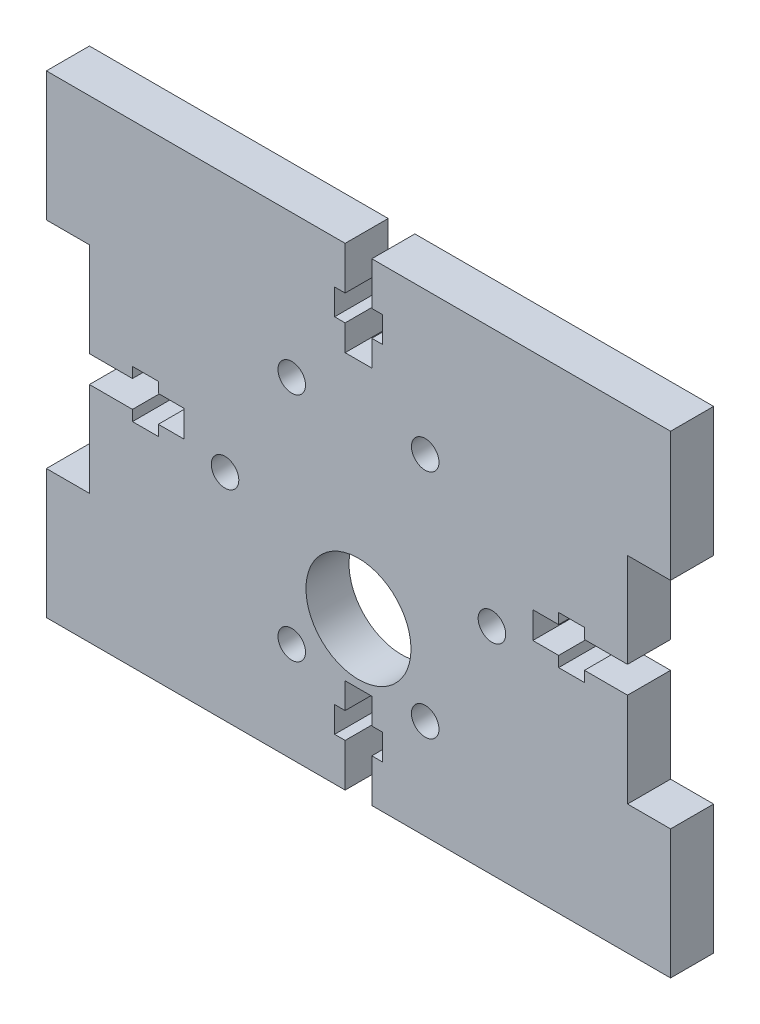
SolidWorks part; units mm, degrees
ref_plane "Plan de face" through (0, 0, 0) normal (0, 0, 1) x (1, 0, 0)
ref_plane "Plan de dessus" through (0, 0, 0) normal (0, 1, 0) x (1, 0, 0)
ref_plane "Plan de droite" through (0, 0, 0) normal (1, 0, 0) x (0, 0, -1)
ref_plane "Plan1" through (0, 0, 0) normal (0, 0, -1) x (-1, 0, 0)
sketch "Esquisse1" plane through (0, 0, 0) normal (0, 0, -1) x (-1, 0, 0)
  line L0 (-4.9964, 30) -> (-31.25, 30)
  line L1 (-31.25, 30) -> (-31.25, -25)
  line L2 (-31.25, -25) -> (-4.9964, -25)
  line L3 (-4.9964, -25) -> (-4.9964, 30)
extrude "Boss.-Extru.1" add sketch "Esquisse1" against normal blind 5
sketch "Esquisse2" plane through (31.25, 0, 0) normal (1, 0, 0) x (0, 0, -1)
  line L0 (0, 15) -> (-2.05, 15)
  line L1 (-2.05, 15) -> (-5, 17.95)
  line L2 (-5, 17.95) -> (-5, 30)
  line L3 (-5, 30) -> (0, 30)
  line L4 (0, 30) -> (0, 15)
extrude "Boss.-Extru.2" add sketch "Esquisse2" along normal blind 5
sketch "Esquisse3" plane through (31.25, 0, 0) normal (1, 0, 0) x (0, 0, -1)
  line L0 (-5, -12.95) -> (-2.05, -10)
  line L1 (-2.05, -10) -> (0, -10)
  line L2 (0, -10) -> (0, -25)
  line L3 (0, -25) -> (-5, -25)
  line L4 (-5, -25) -> (-5, -12.95)
extrude "Boss.-Extru.3" add sketch "Esquisse3" along normal blind 5
sketch "Esquisse4" plane through (0, 30, 0) normal (0, 1, 0) x (-1, 0, 0)
  line L0 (-4.9964, 5) -> (-7.9464, 5)
  line L1 (-7.9464, 5) -> (-4.9964, 2.05)
  line L2 (-4.9964, 2.05) -> (-4.9964, 5)
extrude "Enlèv. mat.-Extru.1" cut sketch "Esquisse4" against normal blind 5
sketch "Esquisse5" plane through (4.9964, 0, 0) normal (-1, 0, 0) x (0, 0, 1)
  line L0 (0, -25) -> (0, 25)
  line L1 (0, 25) -> (5, 25)
  line L2 (5, 25) -> (5, -25)
  line L3 (5, -25) -> (0, -25)
extrude "Boss.-Extru.4" add sketch "Esquisse5" along normal blind 36.2464
sketch "Esquisse6" plane through (-31.25, 0, 0) normal (-1, 0, 0) x (0, 0, 1)
  line L0 (0, -25) -> (0, -10)
  line L1 (0, -10) -> (2.05, -10)
  line L2 (2.05, -10) -> (5, -12.95)
  line L3 (5, -12.95) -> (5, -25)
  line L4 (5, -25) -> (0, -25)
extrude "Boss.-Extru.5" add sketch "Esquisse6" along normal blind 5
sketch "Esquisse7" plane through (-31.25, 0, 0) normal (-1, 0, 0) x (0, 0, 1)
  line L0 (0, 25) -> (5, 25)
  line L1 (5, 25) -> (5, 17.95)
  line L2 (5, 17.95) -> (2.05, 15)
  line L3 (2.05, 15) -> (0, 15)
  line L4 (0, 15) -> (0, 25)
extrude "Boss.-Extru.6" add sketch "Esquisse7" along normal blind 5
sketch "Esquisse8" plane through (0, 25, 0) normal (0, 1, 0) x (-1, 0, 0)
  line L0 (5.0006, 2.0542) -> (7.9464, 5)
  line L1 (7.9464, 5) -> (36.25, 5)
  line L2 (36.25, 5) -> (36.25, 0)
  line L3 (36.25, 0) -> (5.0006, 0)
  line L4 (5.0006, 0) -> (5.0006, 2.0542)
extrude "Boss.-Extru.7" add sketch "Esquisse8" along normal blind 5
hole_wizard "Diamètre du perçage Ø12.2 (12.2)1" positions "Esquisse10" profile "Esquisse9" hole size "Ø12.2" standard "Ansi Metric"
sketch "Esquisse10" plane through (0, 0, 5) normal (0, 0, 1) x (1, 0, 0)
  point P0 (0, -7)
sketch "Esquisse9" plane through (0, -7, 5) normal (1, 0, 0) x (0, -1, 0)
  line L0 (0, 0) -> (0, 5)
  line L1 (0, 5) -> (6.1, 5)
  line L2 (6.1, 5) -> (6.1, 0)
  line L5 (6.1, 0) -> (0, 0)
  line L11 (0, -6.35) -> (0, 107.95) construction
  dimension "Diamètre du perçage jusqu'au prochain" = 12.2
  dimension "Profondeur du perçage jusqu'au prochain" = 5
hole_wizard "Diamètre du perçage Ø3.2 (3.2)1" positions "Esquisse12" profile "Esquisse11" hole size "Ø3.2" standard "Ansi Metric" end condition through all
sketch "Esquisse12" plane through (0, 0, 5) normal (0, 0, 1) x (1, 0, 0)
  point P0 (-7.75, -13.4234)
  point P1 (15.5, 0)
  point P2 (-7.75, 13.4234)
  point P3 (7.75, 13.4234)
  point P4 (7.75, -13.4234)
  point P5 (-15.5, 0)
sketch "Esquisse11" plane through (-7.75, -13.4234, 5) normal (1, 0, 0) x (0, -1, 0)
  line L0 (0, 0) -> (0, 5)
  line L1 (0, 5) -> (1.6, 5)
  line L2 (1.6, 5) -> (1.6, 0)
  line L5 (1.6, 0) -> (0, 0)
  line L11 (0, -6.35) -> (0, 107.95) construction
  dimension "Diamètre du perçage jusqu'au prochain" = 3.2
  dimension "Profondeur du perçage jusqu'au prochain" = 5
fillet "Congé1" radius 1.6 6 edges at (4.9964, 27.5, 2.05) (33.75, -10, 2.05) (33.75, 15, 2.05) (-33.75, -10, 2.05) (-5.0006, 27.5, 2.0542) (-33.75, 15, 2.05) tangent propagation no
sketch "Esquisse13" plane through (0, 0, 5) normal (0, 0, 1) x (1, 0, 0)
  line L1 (-36.25, 17.95) -> (-31.25, 17.95)
  line L2 (-36.25, 17.95) -> (-36.25, 15)
  line L3 (-36.25, 15) -> (-31.25, 15)
  line L4 (-31.25, 17.95) -> (-31.25, 15)
  line L5 (-36.25, -10) -> (-31.25, -10)
  line L6 (-36.25, -10) -> (-36.25, -12.95)
  line L7 (-36.25, -12.95) -> (-31.25, -12.95)
  line L8 (-31.25, -10) -> (-31.25, -12.95)
  line L9 (-7.9464, 30) -> (-5.0006, 30)
  line L10 (-7.9464, 30) -> (-7.9464, 25)
  line L11 (-7.9464, 25) -> (-5.0006, 25)
  line L12 (-5.0006, 30) -> (-5.0006, 25)
  line L13 (4.9964, 30) -> (7.9464, 30)
  line L14 (4.9964, 30) -> (4.9964, 25)
  line L15 (4.9964, 25) -> (7.9464, 25)
  line L16 (7.9464, 30) -> (7.9464, 25)
  line L17 (31.25, 17.95) -> (36.25, 17.95)
  line L18 (31.25, 17.95) -> (31.25, 15)
  line L19 (31.25, 15) -> (36.25, 15)
  line L20 (36.25, 17.95) -> (36.25, 15)
  line L21 (31.25, -10) -> (36.25, -10)
  line L22 (31.25, -10) -> (31.25, -12.95)
  line L23 (31.25, -12.95) -> (36.25, -12.95)
  line L24 (36.25, -10) -> (36.25, -12.95)
  line L25 (-5.0006, 30) -> (4.9964, 30)
  line L26 (-5.0006, 30) -> (-5.0006, 25)
  line L27 (-5.0006, 25) -> (4.9964, 25)
  line L28 (4.9964, 30) -> (4.9964, 25)
  line M9 (7.9464, 30) -> (7.9464, 25)
  line M10 (7.9464, 25) -> (-7.9464, 25)
  line M11 (-7.9464, 25) -> (-7.9464, 30)
  line M14 (-36.25, 17.95) -> (-31.25, 17.95)
  line M15 (-31.25, 17.95) -> (-31.25, -12.95)
  line M16 (-31.25, -12.95) -> (-36.25, -12.95)
  line M20 (36.25, -12.95) -> (31.25, -12.95)
  line M21 (31.25, -12.95) -> (31.25, 17.95)
  line M22 (31.25, 17.95) -> (36.25, 17.95)
extrude "Boss.-Extru.8" add sketch "Esquisse13" against normal blind 5 contours L25 L12 L14 M10 | L12 L9 M11 M10 | L13 L14 M10 M9 | L20 L19 M22 M21 | L24 L21 M21 M20 | L5 L6 M16 M15 | L2 L3 M15 M14 region at (-33.75, -11.475, 5) region at (-33.75, 16.475, 5) region at (-6.4735, 27.5, 5) region at (-0.0021, 27.5, 5) region at (6.4714, 27.5, 5) region at (33.75, -11.475, 5) region at (33.75, 16.475, 5)
sketch "Esquisse14" plane through (0, 0, 5) normal (0, 0, 1) x (1, 0, 0)
  line L0 (1.55, 19) -> (-1.55, 19)
  line L1 (1.55, 19) -> (1.55, 30)
  line L2 (1.55, 30) -> (-1.55, 30)
  line L3 (-1.55, 19) -> (-1.55, 30)
  line L4 (2.78, 22) -> (-2.77, 22)
  line L5 (2.78, 22) -> (2.78, 25)
  line L6 (2.78, 25) -> (-2.77, 25)
  line L7 (-2.77, 22) -> (-2.77, 25)
  line L8 (-20.25, 0.95) -> (-31.25, 0.95)
  line L9 (-20.25, 0.95) -> (-20.25, 4.05)
  line L10 (-20.25, 4.05) -> (-31.25, 4.05)
  line L11 (-31.25, 0.95) -> (-31.25, 4.05)
  line L12 (-23.25, -0.28) -> (-26.25, -0.28)
  line L13 (-23.25, -0.28) -> (-23.25, 5.27)
  line L14 (-23.25, 5.27) -> (-26.25, 5.27)
  line L15 (-26.25, -0.28) -> (-26.25, 5.27)
  line L18 (-36.25, 30) -> (36.25, 30) construction
  line L19 (-31.25, -10) -> (-31.25, 15) construction
  line L20 (-31.25, -10) -> (-36.25, -10) construction
  line L21 (0, 0) -> (0, 11.8782) construction
  line L22 (26.25, -0.28) -> (26.25, 5.27)
  line L23 (23.25, 5.27) -> (26.25, 5.27)
  line L24 (23.25, -0.28) -> (23.25, 5.27)
  line L25 (23.25, -0.28) -> (26.25, -0.28)
  line L26 (31.25, 0.95) -> (31.25, 4.05)
  line L27 (20.25, 4.05) -> (31.25, 4.05)
  line L28 (20.25, 0.95) -> (20.25, 4.05)
  line L29 (20.25, 0.95) -> (31.25, 0.95)
  line L30 (36.25, 30) -> (36.25, 15) construction
  line L31 (20.25, 2.5) -> (-20.25, 2.5) construction
  line L32 (-2.77, -17) -> (-2.77, -20)
  line L33 (2.78, -20) -> (-2.77, -20)
  line L34 (2.78, -17) -> (2.78, -20)
  line L35 (2.78, -17) -> (-2.77, -17)
  line L36 (-1.55, -14) -> (-1.55, -25)
  line L37 (1.55, -25) -> (-1.55, -25)
  line L38 (1.55, -14) -> (1.55, -25)
  line L39 (1.55, -14) -> (-1.55, -14)
  line M16 (-31.25, 15) -> (-31.25, -10)
  line M19 (-36.25, -25) -> (36.25, -25)
  dimension "D1" = 3
  dimension "D2" = 5
  dimension "D3" = 5.55
  dimension "D4" = 3.1
  dimension "D5" = 1.23
  dimension "D6" = 11
  dimension "D7" = 3
  dimension "D8" = 5
  dimension "D9" = 5.55
  dimension "D10" = 3.1
  dimension "D11" = 1.23
  dimension "D12" = 0
  dimension "D13" = 34.7
  dimension "D14" = 0
  dimension "D15" = 10.95
  dimension "D16" = 3
extrude "Enlèv. mat.-Extru.2" cut sketch "Esquisse14" against normal blind 5 contours L8 L15 L10 M16 | L15 L8 L13 L10 | L15 L12 L13 L8 | L13 L8 L9 L10 | L15 L10 L13 L14 | L7 L4 L3 L6 | L1 L6 L3 L4 | L6 L1 L3 | L5 L6 L1 L4 | L1 L4 L3 L0 | L28 L29 L24 L27 | L24 L29 L22 L27 | L29 L24 L25 L22 | L24 L27 L22 L23 | L38 L33 L36 M19 | L38 L35 L36 L33 | L36 L35 L32 L33 | L38 L39 L36 L35 | L35 L38 L33 L34 | L29 L26 L27 L28 region at (0, 20.5, 5) region at (0, 23.5, 5) region at (2.165, 23.5, 5) region at (-2.16, 23.5, 5) region at (0, 27.5, 5) region at (-21.75, 2.5, 5) region at (-24.75, 0.335, 5) region at (-24.75, 2.5, 5) region at (-28.75, 2.5, 5) region at (-24.75, 4.66, 5) region at (24.75, 0.335, 5) region at (24.75, 2.5, 5) region at (24.75, 4.66, 5) region at (21.75, 2.5, 5) region at (-2.16, -18.5, 5) region at (0, -15.5, 5) region at (0, -18.5, 5) region at (0, -22.5, 5) region at (2.165, -18.5, 5)
